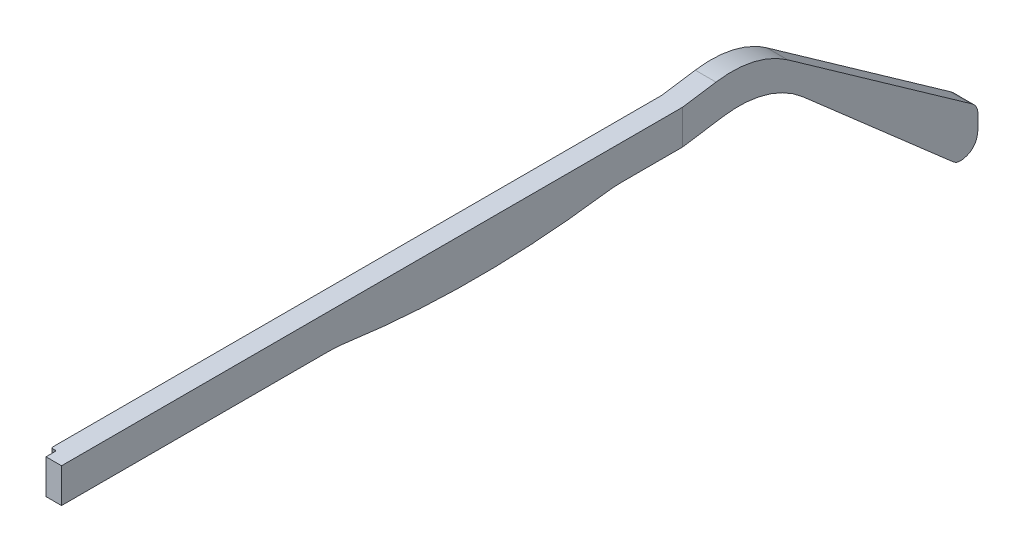
SolidWorks part; units mm, degrees
ref_plane "Front Plane" through (0, 0, 0) normal (0, 0, 1) x (1, 0, 0)
ref_plane "Top Plane" through (0, 0, 0) normal (0, 1, 0) x (1, 0, 0)
ref_plane "Right Plane" through (0, 0, 0) normal (1, 0, 0) x (0, 0, -1)
sketch "Sketch2" plane through (0, 0, 0) normal (0, 1, 0) x (1, 0, 0)
  line L0 (0, 0) -> (0, 90)
  line L1 (0, 90) -> (0, 140) construction
  line L3 (-3, 0) -> (0, 0)
  line L5 (0, 90) -> (-6.4875, 139.2772)
  line L6 (-6.4875, 139.2772) -> (-9.4875, 139.2772)
  line L7 (-9.4875, 139.2772) -> (-3, 90)
  line L8 (-3, 90) -> (-3, 0)
  dimension "D1" = 90
  dimension "D2" = 50
  dimension "D3" = 3
  dimension "D4" = 7.5
  dimension "D5" = 6.4875
extrude "Boss-Extrude1" add sketch "Sketch2" against normal blind 33
sketch "Sketch3" plane through (0, 0, 0) normal (1, 0, 0) x (0, 0, -1)
  line L0 (0, 0) -> (0, -5)
  line L1 (0, -33) -> (0, 0) construction
  line L2 (0, -5) -> (38.5524, -5)
  line L3 (40, -6.5) -> (80, -6.5) construction
  line L4 (81.4476, -5) -> (90, -5)
  line L5 (90, -33) -> (90, 0) construction
  line L6 (90, -5) -> (96.7662, -5)
  line L7 (110.0726, -10.0688) -> (135.8038, -33)
  line L8 (90, -33) -> (139.2772, -33) construction
  line L9 (0, 0) -> (40, 0)
  line L10 (0, 0) -> (90, 0) construction
  line L11 (40, 0) -> (80, 0)
  line L12 (80, 0) -> (90, 0)
  line L13 (90, 0) -> (95.5526, 0)
  line L14 (90, 0) -> (139.2772, 0) construction
  line L15 (107.507, -3.9659) -> (139.2772, -27.6526)
  line L16 (139.2772, -33) -> (139.2772, 0) construction
  line L17 (104.3849, -5) -> (108.894, -5) construction
  line L18 (108.894, -5) -> (106.898, -7.2397) construction
  line L19 (90, -33) -> (139.2772, -33)
  line L20 (139.2772, -33) -> (139.2772, 0)
  line L21 (90, 0) -> (139.2772, 0)
  line L25 (90, 0) -> (0, 0)
  line L26 (0, 0) -> (0, -33)
  line L27 (0, -33) -> (90, -33)
  line L28 (90, -33) -> (90, 0)
  line L29 (90, 0) -> (0, 0)
  line L30 (0, 0) -> (0, -33)
  line L31 (0, -33) -> (90, -33)
  line L32 (90, -33) -> (90, 0) construction
  arc A0 (41.3363, -5.1947) -> (78.6637, -5.1947) centre (60, 127.5833) ccw
  arc A1 (95.5526, 0) -> (107.507, -3.9659) centre (95.5526, -20) cw
  arc A2 (96.7662, -5) -> (110.0726, -10.0688) centre (96.7662, -25) cw
  arc A3 (81.4476, -5) -> (78.6637, -5.1947) centre (81.4476, -25) ccw
  arc A4 (38.5524, -5) -> (41.3363, -5.1947) centre (38.5524, -25) cw
  point P32 (102.1877, 0)
  point P38 (80, -5)
  point P41 (40, -5)
  line M11 (0, 0) -> (0, -33)
  line M12 (0, -33) -> (90, -33)
  line M13 (90, -33) -> (90, 0)
  dimension "D7" = 20
  dimension "D1" = 5
  dimension "D2" = 40
  dimension "D3" = 6.5
  dimension "D4" = 10
  dimension "D5" = 5
  dimension "D6" = 3
  dimension "D8" = 0
extrude "Cut-Extrude1" cut sketch "Sketch3" against normal through all contours A4 L2 L4 A3 A0 M11 M12 M13 | A2 L6 L19 L7 M13 | L21 A1 L15 L20 region at (0, -19.2169, -44.7572) region at (0, -21.5611, -106.4336) region at (0, -9.1433, -126.6932)
fillet "Fillet2" radius 3 3 edges at (-7.5302, -33, -135.8038) (-7.9875, -33, -139.2772) (-7.9875, -27.6526, -139.2772) curvature continuous yes
sketch "Sketch4" plane through (0, -0.5, 0) normal (0, 1, 0) x (1, 0, 0)
  line L1 (-3, 0) -> (-2.25, 0)
  line L2 (-3, 0) -> (-3, 1.5)
  line L3 (-3, 1.5) -> (-2.25, 1.5)
  line L4 (-2.25, 0) -> (-2.25, 1.5)
  dimension "D1" = 0.75
  dimension "D2" = 1.5
extrude "Cut-Extrude2" cut sketch "Sketch4" against normal through all both and the other way through all
fillet "Fillet3" radius 0.25 2 edges at (-2.25, -2.5, -1.5) (-3, -2.5, -1.5) curvature continuous yes
